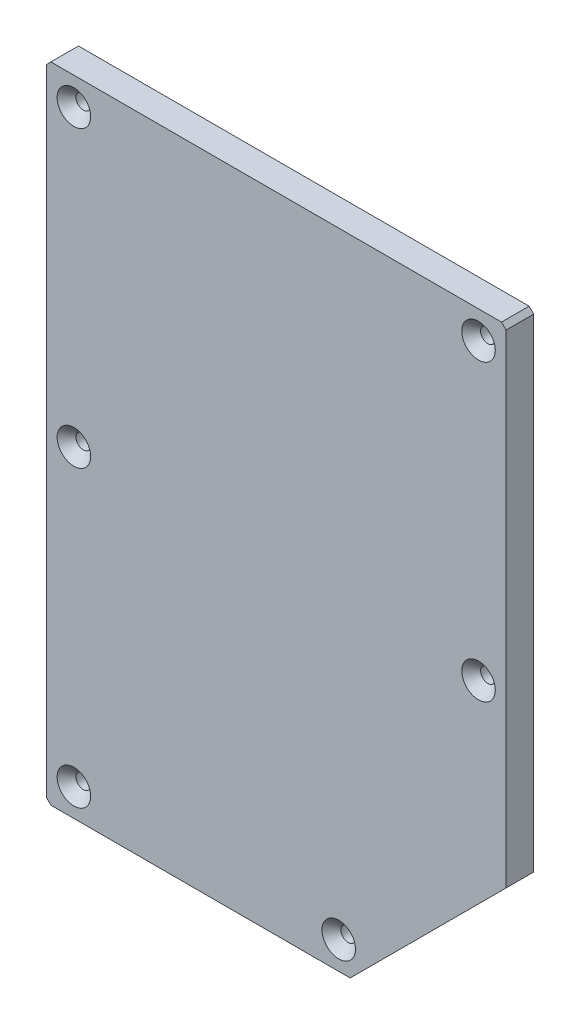
SolidWorks part; units mm, degrees
ref_plane "Front Plane" through (0, 0, 0) normal (0, 0, 1) x (1, 0, 0)
ref_plane "Top Plane" through (0, 0, 0) normal (0, 1, 0) x (1, 0, 0)
ref_plane "Right Plane" through (0, 0, 0) normal (1, 0, 0) x (0, 0, -1)
sketch "Sketch1" plane through (0, 0, 0) normal (0, 0, 1) x (1, 0, 0)
  line L8 (60, -62.4854) -> (60, 42.5997)
  line L9 (60, 42.5997) -> (59, 43.5997)
  line L10 (59, 43.5997) -> (-39, 43.5997)
  line L11 (-39, 43.5997) -> (-40, 42.5997)
  line L12 (-40, 42.5997) -> (-40, -95.4003)
  line L13 (-40, -95.4003) -> (-39, -96.4003)
  line L14 (-39, -96.4003) -> (26.0851, -96.4003)
  line L15 (26.0851, -96.4003) -> (60, -62.4854)
  line L16 (60, -62.4854) -> (60, 42.5997)
  line L17 (60, 42.5997) -> (59, 43.5997)
  line L18 (59, 43.5997) -> (-39, 43.5997)
  line L19 (-39, 43.5997) -> (-40, 42.5997)
  line L20 (-40, 42.5997) -> (-40, -95.4003)
  line L21 (-40, -95.4003) -> (-39, -96.4003)
  line L22 (-39, -96.4003) -> (26.0851, -96.4003)
  line L23 (26.0851, -96.4003) -> (60, -62.4854)
  dimension "D1" = 0
extrude "Boss-Extrude1" add sketch "Sketch1" along normal blind 6
hole_wizard "CSK for M3 Countersunk Flat Head Screw1" positions "3DSketch1" profile "Sketch4" countersink size "M3" standard "ISO" end condition up to next
sketch3d "3DSketch1"
  point P0 (-34, 37.5997, 6)
  point P2 (54, 37.5997, 6)
  point P4 (54, -26.4003, 6)
  point P18 (23.5999, -90.4003, 6)
  point P20 (-34, -90.4003, 6)
  point P22 (-34, -26.4003, 6)
sketch "Sketch4" plane through (-34, 37.5997, 6) normal (1, 0, 0) x (0, -1, 0)
  line L0 (0, 0) -> (0, 6)
  line L1 (0, 6) -> (1.6, 6)
  line L2 (1.6, 6) -> (1.6, 2.05)
  line L3 (1.6, 2.05) -> (3.65, 0)
  line L5 (3.65, 0) -> (0, 0)
  line L6 (-1.6, 2.05) -> (-3.65, 0) construction
  line L11 (0, -6.35) -> (0, 107.95) construction
  dimension "Thru Hole Dia." = 3.2
  dimension "Thru Hole Depth" = 6
  dimension "Near C'Sink Dia." = 7.3
  dimension "Near C'Sink Angle" = 90
